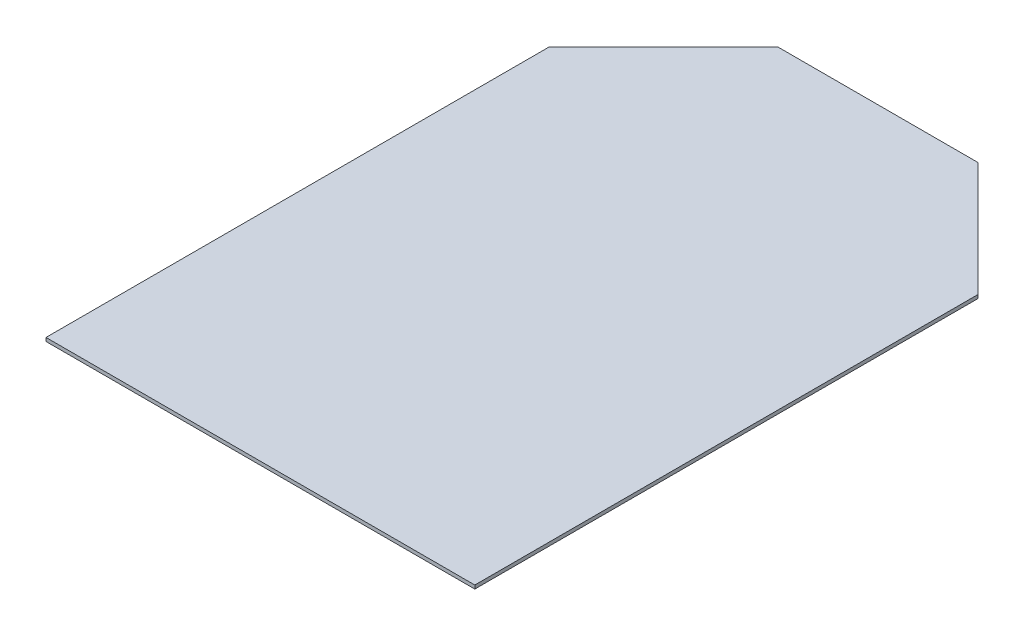
SolidWorks part; units mm, degrees
ref_plane "Front Plane" through (0, 0, 0) normal (0, 0, 1) x (1, 0, 0)
ref_plane "Top Plane" through (0, 0, 0) normal (0, 1, 0) x (1, 0, 0)
ref_plane "Right Plane" through (0, 0, 0) normal (1, 0, 0) x (0, 0, -1)
sketch "BaseSketch" plane through (0, 0, 0) normal (0, 1, 0) x (1, 0, 0)
  line L0 (101.6, 317.5) -> (215.9, 203.2) construction
  line L1 (-139.7, -317.5) -> (139.7, -317.5)
  line L2 (-215.9, -190.5) -> (-215.9, 317.5)
  line L3 (-215.9, 317.5) -> (215.9, 317.5)
  line L4 (215.9, -190.5) -> (215.9, 317.5)
  line L5 (-215.9, -317.5) -> (215.9, 317.5) construction
  line L6 (-215.9, 317.5) -> (215.9, -317.5) construction
  line L7 (215.9, -190.5) -> (139.7, -190.5)
  line L8 (139.7, -190.5) -> (139.7, -317.5)
  line L9 (139.7, -317.5) -> (-139.7, -317.5)
  line L10 (-139.7, -317.5) -> (-139.7, -190.5)
  line L11 (-139.7, -190.5) -> (-215.9, -190.5)
  line L12 (215.9, -190.5) -> (215.9, -317.5) construction
  line L13 (215.9, -317.5) -> (139.7, -317.5) construction
  line L14 (-139.7, -317.5) -> (-215.9, -317.5) construction
  line L15 (-215.9, -317.5) -> (-215.9, -190.5) construction
  line L16 (-215.9, 203.2) -> (-101.6, 317.5) construction
  line L17 (0, -2.0955) -> (0, 2.0955) construction
  point P0 (0, 0)
  dimension "D1" = 90
extrude "Boss-Extrude1" add sketch "BaseSketch" along normal blind 3.81 contours L11 L10 L1 L8 L7 L4 L3 L2 region at (0, 0, -19.2911)
sketch "Sketch7" plane through (0, 3.81, 0) normal (0, 1, 0) x (1, 0, 0)
  line L1 (-215.9, 317.5) -> (215.9, 317.5) construction
  line L2 (-215.9, -190.5) -> (-215.9, 317.5) construction
  line L3 (-139.7, -317.5) -> (139.7, -317.5) construction
  line L4 (215.9, -190.5) -> (215.9, 317.5) construction
  line L12 (230.9, -332.5) -> (230.9, 332.5)
  line L13 (230.9, 332.5) -> (-230.9, 332.5)
  line L14 (-230.9, 332.5) -> (-230.9, -332.5)
  line L15 (-230.9, -332.5) -> (230.9, -332.5)
  dimension "D1" = 15
  dimension "D2" = 15
  dimension "D3" = 15
  dimension "D4" = 15
extrude "Boss-Extrude2" add sketch "Sketch7" against normal up to surface (3.81 mm away) up to face at (0, 0, 95.25)
sketch "Sketch8" plane through (0, 3.81, 0) normal (0, 1, 0) x (1, 0, 0)
  line L0 (-230.9, 332.5) -> (-230.9, 209.4132)
  line L1 (-230.9, 332.5) -> (-230.9, -332.5) construction
  line L2 (-230.9, 209.4132) -> (-107.8132, 332.5)
  line L3 (230.9, 332.5) -> (-230.9, 332.5) construction
  line L4 (-107.8132, 332.5) -> (-230.9, 332.5)
  line L5 (107.8132, 332.5) -> (230.9, 209.4132)
  line L6 (230.9, -332.5) -> (230.9, 332.5) construction
  line L7 (230.9, 209.4132) -> (230.9, 332.5)
  line L8 (230.9, 332.5) -> (107.8132, 332.5)
  line L9 (-215.9, 203.2) -> (-101.6, 317.5) construction
  line L10 (101.6, 317.5) -> (215.9, 203.2) construction
  dimension "D1" = 15
  dimension "D2" = 15
extrude "Cut-Extrude1" cut sketch "Sketch8" against normal through all
